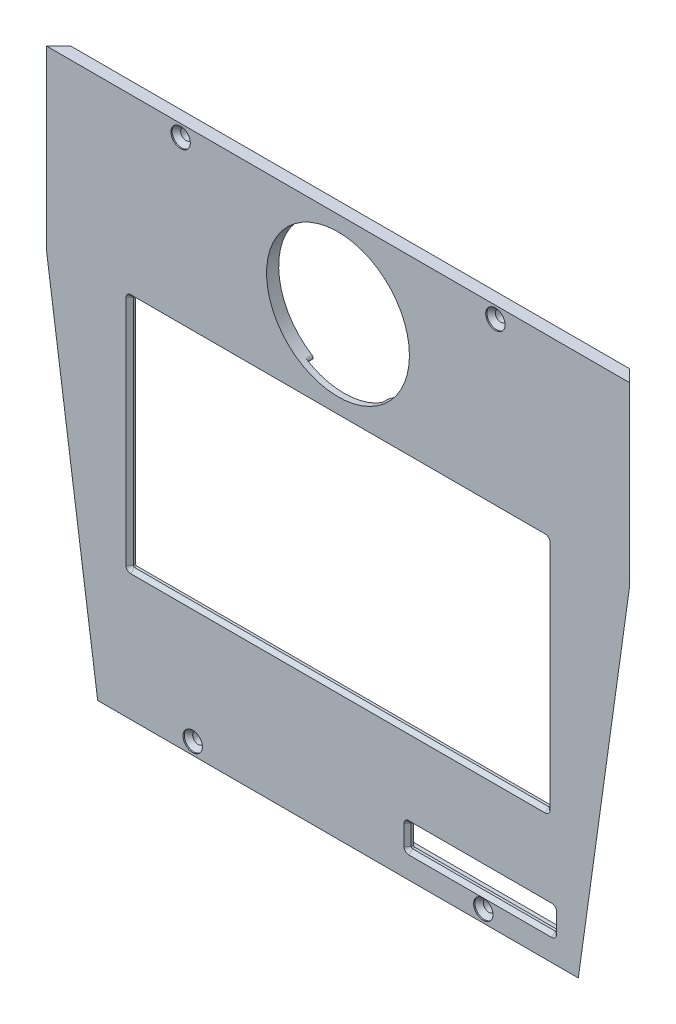
SolidWorks part; units mm, degrees
material "Oak"
ref_plane "Front Plane" through (0, 0, 0) normal (0, 0, 1) x (1, 0, 0)
ref_plane "Top Plane" through (0, 0, 0) normal (0, 1, 0) x (1, 0, 0)
ref_plane "Right Plane" through (0, 0, 0) normal (1, 0, 0) x (0, 0, -1)
sketch "Sketch1" plane through (0, 0, 5) normal (0, 0, 1) x (1, 0, 0)
  line L4 (57.5, 1) -> (177.5, 1)
  line L5 (177.5, 1) -> (177.5, 19.5)
  line L6 (177.5, 19.5) -> (57.5, 19.5)
  line L7 (57.5, 19.5) -> (57.5, 1)
  line L8 (57.5, 1) -> (177.5, 1)
  line L9 (177.5, 1) -> (177.5, 19.5)
  line L10 (177.5, 19.5) -> (57.5, 19.5)
  line L11 (57.5, 19.5) -> (57.5, 1)
  line L12 (-172.1, 87.35) -> (172.1, 87.35)
  line L13 (-172.1, 280.95) -> (-172.1, 87.35)
  line L14 (172.1, 280.95) -> (-172.1, 280.95)
  line L15 (172.1, 87.35) -> (172.1, 280.95)
  line L16 (-172.1, 87.35) -> (172.1, 87.35)
  line L17 (-172.1, 280.95) -> (-172.1, 87.35)
  line L18 (172.1, 280.95) -> (-172.1, 280.95)
  line L19 (172.1, 87.35) -> (172.1, 280.95)
  line L22 (-198.5, -20) -> (198.5, -20)
  line L23 (198.5, -20) -> (240.8028, 281)
  line L24 (240.8028, 281) -> (240.8028, 427)
  line L25 (240.8028, 427) -> (-240.8028, 427)
  line L26 (-240.8028, 427) -> (-240.8028, 281)
  line L27 (-240.8028, 281) -> (-198.5, -20)
  line L28 (-198.5, -20) -> (198.5, -20)
  line L29 (198.5, -20) -> (240.8028, 281)
  line L30 (240.8028, 281) -> (240.8028, 427)
  line L31 (240.8028, 427) -> (-240.8028, 427)
  line L32 (-240.8028, 427) -> (-240.8028, 281)
  line L33 (-240.8028, 281) -> (-198.5, -20)
  circle A1 centre (0, 355.5) radius 40
  circle A2 centre (0, 355.5) radius 40
  dimension "D1" = 0
  dimension "D2" = 0
  dimension "D3" = 0
  dimension "D4" = 0
extrude "Boss-Extrude1" add sketch "Sketch1" along normal mid plane 10
sketch "Sketch2" plane through (0, 0, 0) normal (0, 0, -1) x (-1, 0, 0)
  line L6 (196, 68.5) -> (-196, 68.5)
  line L7 (196, 34.0645) -> (196, 68.5)
  line L8 (191.072, -1) -> (196, 34.0645)
  line L9 (-191.072, -1) -> (191.072, -1)
  line L10 (-196, 34.0645) -> (-191.072, -1)
  line L11 (-196, 68.5) -> (-196, 34.0645)
  line L13 (196, 34.0645) -> (196, 68.5)
  line L14 (191.072, -1) -> (196, 34.0645)
  line L15 (-191.072, -1) -> (191.072, -1)
  line L16 (-196, 34.0645) -> (-191.072, -1)
  line L17 (-196, 68.5) -> (-196, 34.0645)
  line L42 (-183.3, 300) -> (183.3, 300) construction
  line L44 (-196, 68.5) -> (-196, 297)
  line L45 (-191, 302) -> (191, 302)
  line L46 (196, 68.5) -> (196, 297)
  arc A0 (191, 302) -> (196, 297) centre (191, 297) cw
  arc A1 (-196, 297) -> (-191, 302) centre (-191, 297) cw
  dimension "D3" = 5
  dimension "D2" = 2
  dimension "D1" = 0
extrude "Cut-Extrude1" cut sketch "Sketch2" against normal blind 5
sketch "Sketch3" plane through (0, 0, 10) normal (0, 0, 1) x (1, 0, 0)
  circle A0 centre (0, 355.5) radius 59
  dimension "D1" = 118
extrude "Cut-Extrude2" cut sketch "Sketch3" against normal through all
fillet "Fillet1" radius 1 8 edges at (57.5, 1, 7.5) (57.5, 19.5, 7.5) (177.5, 19.5, 7.5) (177.5, 1, 7.5) (172.1, 87.35, 7.5) (172.1, 280.95, 7.5) (-172.1, 280.95, 7.5) (-172.1, 87.35, 7.5)
fillet "Fillet2" radius 2 2 edges at (-24.8747, 302, 2.5) (24.8747, 302, 2.5)
chamfer "Chamfer1" distance 3 angle 45 16 edges at (117.5, 19.5, 10) (57.7929, 19.2071, 10) (177.2071, 19.2071, 10) (57.5, 10.25, 10) (177.5, 10.25, 10) (57.7929, 1.2929, 10) (177.2071, 1.2929, 10) (117.5, 1, 10) (172.1, 184.15, 10) (171.8071, 280.6571, 10) (171.8071, 87.6429, 10) (0, 280.95, 10) (0, 87.35, 10) (-171.8071, 280.6571, 10) (-171.8071, 87.6429, 10) (-172.1, 184.15, 10)
chamfer "Chamfer2" distance 10 angle 45 4 edges at (219.6514, 130.5, 0) (240.8028, 354, 0) (-219.6514, 130.5, 0) (-240.8028, 354, 0)
hole_wizard "CSK for M8 Hex Socket Countersunk Head Screw1" positions "Sketch4" profile "Sketch5" countersink size "M8" standard "DIN" end condition through all
sketch "Sketch4" plane through (0, 0, 10) normal (0, 0, 1) x (1, 0, 0)
  point P0 (-130, 417)
  point P7 (130, 417)
  point P10 (120, -10)
  point P16 (-120, -10)
sketch "Sketch5" plane through (-130, 417, 10) normal (1, 0, 0) x (0, -1, 0)
  line L0 (0, 0) -> (0, 10)
  line L1 (0, 10) -> (4.5, 10)
  line L2 (4.5, 10) -> (4.5, 4.5)
  line L3 (4.5, 4.5) -> (8, 1)
  line L4 (8, 1) -> (8, 0)
  line L6 (8, 0) -> (0, 0)
  line L7 (-4.5, 4.5) -> (-8, 1) construction
  line L11 (0, -6.35) -> (0, 107.95) construction
  dimension "Thru Hole Dia." = 9
  dimension "Thru Hole Depth" = 10
  dimension "C'Sink Dia." = 16
  dimension "C'Sink Angle" = 90
  dimension "Head Clearance" = 1
fillet "Fillet3" radius 5 4 edges at (-196, 34.0645, 2.5) (-191.072, -1, 2.5) (191.072, -1, 2.5) (196, 34.0645, 2.5)
